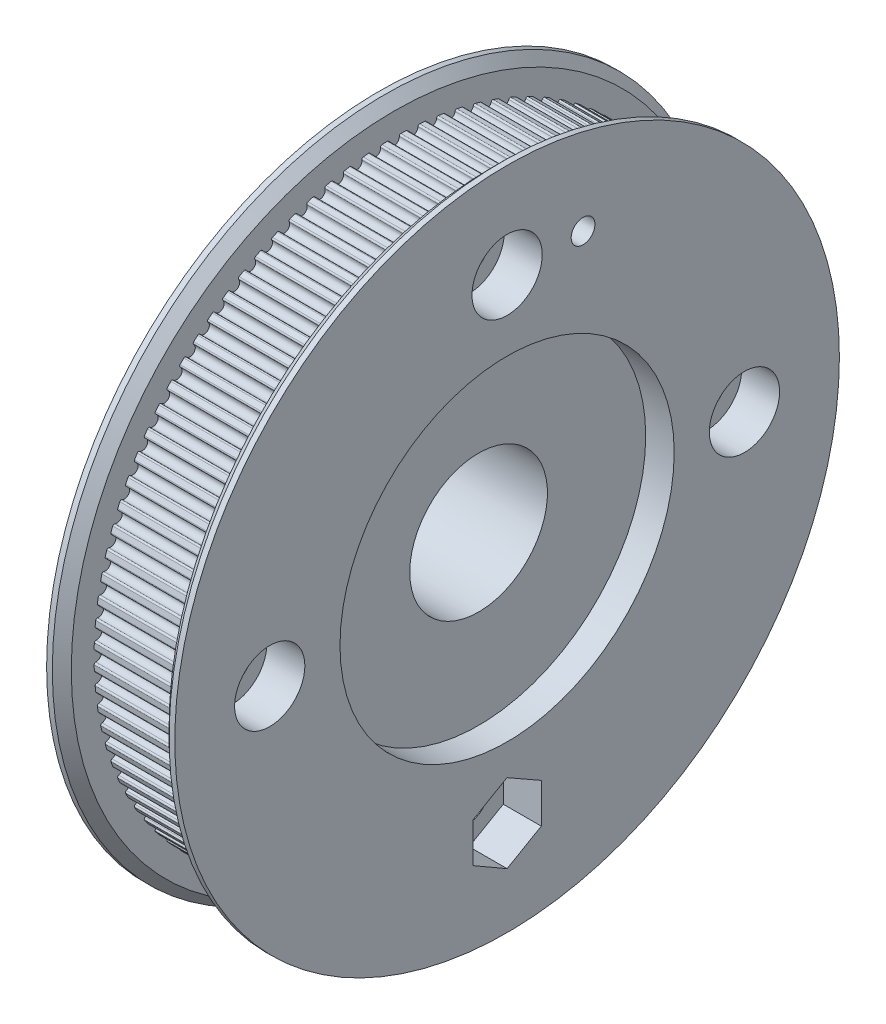
SolidWorks part; units mm, degrees
note: '?' marks a value the reader was unsure of.
ref_plane "Front Plane" through (0, 0, 0) normal (0, 0, 1) x (1, 0, 0)
ref_plane "Top Plane" through (0, 0, 0) normal (0, 1, 0) x (1, 0, 0)
ref_plane "Right Plane" through (0, 0, 0) normal (1, 0, 0) x (0, 0, -1)
sketch "Sketch1" plane through (0, 0, 0) normal (1, 0, 0) x (0, 0, -1)
  circle A0 centre (0, 0) radius 31.6
  circle A1 centre (0, 0) radius 7.25
  dimension "D1" = 63.2
  dimension "D2" = 14.5
extrude "Boss-Extrude1" add sketch "Sketch1" along normal blind 10.3
sketch "Sketch2" plane through (0, 0, 0) normal (1, 0, 0) x (0, 0, -1)
  circle A0 centre (0, 0) radius 31.39 construction
  circle A1 centre (0, 31.39) radius 0.55
  circle A2 centre (0, 0) radius 31.39 construction
  circle A3 centre (1.971, 31.3281) radius 0.55
  circle A4 centre (0, 0) radius 31.39 construction
  circle A5 centre (3.9342, 31.1425) radius 0.55
  circle A6 centre (0, 0) radius 31.39 construction
  circle A7 centre (5.8819, 30.834) radius 0.55
  circle A8 centre (0, 0) radius 31.39 construction
  circle A9 centre (7.8064, 30.4038) radius 0.55
  circle A10 centre (0, 0) radius 31.39 construction
  circle A11 centre (9.7, 29.8537) radius 0.55
  circle A12 centre (0, 0) radius 31.39 construction
  circle A13 centre (11.5554, 29.1857) radius 0.55
  circle A14 centre (0, 0) radius 31.39 construction
  circle A15 centre (13.3652, 28.4025) radius 0.55
  circle A16 centre (0, 0) radius 31.39 construction
  circle A17 centre (15.1222, 27.5073) radius 0.55
  circle A18 centre (0, 0) radius 31.39 construction
  circle A19 centre (16.8196, 26.5035) radius 0.55
  circle A20 centre (0, 0) radius 31.39 construction
  circle A21 centre (18.4506, 25.395) radius 0.55
  circle A22 centre (0, 0) radius 31.39 construction
  circle A23 centre (20.0087, 24.1864) radius 0.55
  circle A24 centre (0, 0) radius 31.39 construction
  circle A25 centre (21.4879, 22.8823) radius 0.55
  circle A26 centre (0, 0) radius 31.39 construction
  circle A27 centre (22.8823, 21.4879) radius 0.55
  circle A28 centre (0, 0) radius 31.39 construction
  circle A29 centre (24.1864, 20.0087) radius 0.55
  circle A30 centre (0, 0) radius 31.39 construction
  circle A31 centre (25.395, 18.4506) radius 0.55
  circle A32 centre (0, 0) radius 31.39 construction
  circle A33 centre (26.5035, 16.8196) radius 0.55
  circle A34 centre (0, 0) radius 31.39 construction
  circle A35 centre (27.5073, 15.1222) radius 0.55
  circle A36 centre (0, 0) radius 31.39 construction
  circle A37 centre (28.4025, 13.3652) radius 0.55
  circle A38 centre (0, 0) radius 31.39 construction
  circle A39 centre (29.1857, 11.5554) radius 0.55
  circle A40 centre (0, 0) radius 31.39 construction
  circle A41 centre (29.8537, 9.7) radius 0.55
  circle A42 centre (0, 0) radius 31.39 construction
  circle A43 centre (30.4038, 7.8064) radius 0.55
  circle A44 centre (0, 0) radius 31.39 construction
  circle A45 centre (30.834, 5.8819) radius 0.55
  circle A46 centre (0, 0) radius 31.39 construction
  circle A47 centre (31.1425, 3.9342) radius 0.55
  circle A48 centre (0, 0) radius 31.39 construction
  circle A49 centre (31.3281, 1.971) radius 0.55
  circle A50 centre (0, 0) radius 31.39 construction
  circle A51 centre (31.39, 0) radius 0.55
  circle A52 centre (0, 0) radius 31.39 construction
  circle A53 centre (31.3281, -1.971) radius 0.55
  circle A54 centre (0, 0) radius 31.39 construction
  circle A55 centre (31.1425, -3.9342) radius 0.55
  circle A56 centre (0, 0) radius 31.39 construction
  circle A57 centre (30.834, -5.8819) radius 0.55
  circle A58 centre (0, 0) radius 31.39 construction
  circle A59 centre (30.4038, -7.8064) radius 0.55
  circle A60 centre (0, 0) radius 31.39 construction
  circle A61 centre (29.8537, -9.7) radius 0.55
  circle A62 centre (0, 0) radius 31.39 construction
  circle A63 centre (29.1857, -11.5554) radius 0.55
  circle A64 centre (0, 0) radius 31.39 construction
  circle A65 centre (28.4025, -13.3652) radius 0.55
  circle A66 centre (0, 0) radius 31.39 construction
  circle A67 centre (27.5073, -15.1222) radius 0.55
  circle A68 centre (0, 0) radius 31.39 construction
  circle A69 centre (26.5035, -16.8196) radius 0.55
  circle A70 centre (0, 0) radius 31.39 construction
  circle A71 centre (25.395, -18.4506) radius 0.55
  circle A72 centre (0, 0) radius 31.39 construction
  circle A73 centre (24.1864, -20.0087) radius 0.55
  circle A74 centre (0, 0) radius 31.39 construction
  circle A75 centre (22.8823, -21.4879) radius 0.55
  circle A76 centre (0, 0) radius 31.39 construction
  circle A77 centre (21.4879, -22.8823) radius 0.55
  circle A78 centre (0, 0) radius 31.39 construction
  circle A79 centre (20.0087, -24.1864) radius 0.55
  circle A80 centre (0, 0) radius 31.39 construction
  circle A81 centre (18.4506, -25.395) radius 0.55
  circle A82 centre (0, 0) radius 31.39 construction
  circle A83 centre (16.8196, -26.5035) radius 0.55
  circle A84 centre (0, 0) radius 31.39 construction
  circle A85 centre (15.1222, -27.5073) radius 0.55
  circle A86 centre (0, 0) radius 31.39 construction
  circle A87 centre (13.3652, -28.4025) radius 0.55
  circle A88 centre (0, 0) radius 31.39 construction
  circle A89 centre (11.5554, -29.1857) radius 0.55
  circle A90 centre (0, 0) radius 31.39 construction
  circle A91 centre (9.7, -29.8537) radius 0.55
  circle A92 centre (0, 0) radius 31.39 construction
  circle A93 centre (7.8064, -30.4038) radius 0.55
  circle A94 centre (0, 0) radius 31.39 construction
  circle A95 centre (5.8819, -30.834) radius 0.55
  circle A96 centre (0, 0) radius 31.39 construction
  circle A97 centre (3.9342, -31.1425) radius 0.55
  circle A98 centre (0, 0) radius 31.39 construction
  circle A99 centre (1.971, -31.3281) radius 0.55
  circle A100 centre (0, 0) radius 31.39 construction
  circle A101 centre (0, -31.39) radius 0.55
  circle A102 centre (0, 0) radius 31.39 construction
  circle A103 centre (-1.971, -31.3281) radius 0.55
  circle A104 centre (0, 0) radius 31.39 construction
  circle A105 centre (-3.9342, -31.1425) radius 0.55
  circle A106 centre (0, 0) radius 31.39 construction
  circle A107 centre (-5.8819, -30.834) radius 0.55
  circle A108 centre (0, 0) radius 31.39 construction
  circle A109 centre (-7.8064, -30.4038) radius 0.55
  circle A110 centre (0, 0) radius 31.39 construction
  circle A111 centre (-9.7, -29.8537) radius 0.55
  circle A112 centre (0, 0) radius 31.39 construction
  circle A113 centre (-11.5554, -29.1857) radius 0.55
  circle A114 centre (0, 0) radius 31.39 construction
  circle A115 centre (-13.3652, -28.4025) radius 0.55
  circle A116 centre (0, 0) radius 31.39 construction
  circle A117 centre (-15.1222, -27.5073) radius 0.55
  circle A118 centre (0, 0) radius 31.39 construction
  circle A119 centre (-16.8196, -26.5035) radius 0.55
  circle A120 centre (0, 0) radius 31.39 construction
  circle A121 centre (-18.4506, -25.395) radius 0.55
  circle A122 centre (0, 0) radius 31.39 construction
  circle A123 centre (-20.0087, -24.1864) radius 0.55
  circle A124 centre (0, 0) radius 31.39 construction
  circle A125 centre (-21.4879, -22.8823) radius 0.55
  circle A126 centre (0, 0) radius 31.39 construction
  circle A127 centre (-22.8823, -21.4879) radius 0.55
  circle A128 centre (0, 0) radius 31.39 construction
  circle A129 centre (-24.1864, -20.0087) radius 0.55
  circle A130 centre (0, 0) radius 31.39 construction
  circle A131 centre (-25.395, -18.4506) radius 0.55
  circle A132 centre (0, 0) radius 31.39 construction
  circle A133 centre (-26.5035, -16.8196) radius 0.55
  circle A134 centre (0, 0) radius 31.39 construction
  circle A135 centre (-27.5073, -15.1222) radius 0.55
  circle A136 centre (0, 0) radius 31.39 construction
  circle A137 centre (-28.4025, -13.3652) radius 0.55
  circle A138 centre (0, 0) radius 31.39 construction
  circle A139 centre (-29.1857, -11.5554) radius 0.55
  circle A140 centre (0, 0) radius 31.39 construction
  circle A141 centre (-29.8537, -9.7) radius 0.55
  circle A142 centre (0, 0) radius 31.39 construction
  circle A143 centre (-30.4038, -7.8064) radius 0.55
  circle A144 centre (0, 0) radius 31.39 construction
  circle A145 centre (-30.834, -5.8819) radius 0.55
  circle A146 centre (0, 0) radius 31.39 construction
  circle A147 centre (-31.1425, -3.9342) radius 0.55
  circle A148 centre (0, 0) radius 31.39 construction
  circle A149 centre (-31.3281, -1.971) radius 0.55
  circle A150 centre (0, 0) radius 31.39 construction
  circle A151 centre (-31.39, 0) radius 0.55
  circle A152 centre (0, 0) radius 31.39 construction
  circle A153 centre (-31.3281, 1.971) radius 0.55
  circle A154 centre (0, 0) radius 31.39 construction
  circle A155 centre (-31.1425, 3.9342) radius 0.55
  circle A156 centre (0, 0) radius 31.39 construction
  circle A157 centre (-30.834, 5.8819) radius 0.55
  circle A158 centre (0, 0) radius 31.39 construction
  circle A159 centre (-30.4038, 7.8064) radius 0.55
  circle A160 centre (0, 0) radius 31.39 construction
  circle A161 centre (-29.8537, 9.7) radius 0.55
  circle A162 centre (0, 0) radius 31.39 construction
  circle A163 centre (-29.1857, 11.5554) radius 0.55
  circle A164 centre (0, 0) radius 31.39 construction
  circle A165 centre (-28.4025, 13.3652) radius 0.55
  circle A166 centre (0, 0) radius 31.39 construction
  circle A167 centre (-27.5073, 15.1222) radius 0.55
  circle A168 centre (0, 0) radius 31.39 construction
  circle A169 centre (-26.5035, 16.8196) radius 0.55
  circle A170 centre (0, 0) radius 31.39 construction
  circle A171 centre (-25.395, 18.4506) radius 0.55
  circle A172 centre (0, 0) radius 31.39 construction
  circle A173 centre (-24.1864, 20.0087) radius 0.55
  circle A174 centre (0, 0) radius 31.39 construction
  circle A175 centre (-22.8823, 21.4879) radius 0.55
  circle A176 centre (0, 0) radius 31.39 construction
  circle A177 centre (-21.4879, 22.8823) radius 0.55
  circle A178 centre (0, 0) radius 31.39 construction
  circle A179 centre (-20.0087, 24.1864) radius 0.55
  circle A180 centre (0, 0) radius 31.39 construction
  circle A181 centre (-18.4506, 25.395) radius 0.55
  circle A182 centre (0, 0) radius 31.39 construction
  circle A183 centre (-16.8196, 26.5035) radius 0.55
  circle A184 centre (0, 0) radius 31.39 construction
  circle A185 centre (-15.1222, 27.5073) radius 0.55
  circle A186 centre (0, 0) radius 31.39 construction
  circle A187 centre (-13.3652, 28.4025) radius 0.55
  circle A188 centre (0, 0) radius 31.39 construction
  circle A189 centre (-11.5554, 29.1857) radius 0.55
  circle A190 centre (0, 0) radius 31.39 construction
  circle A191 centre (-9.7, 29.8537) radius 0.55
  circle A192 centre (0, 0) radius 31.39 construction
  circle A193 centre (-7.8064, 30.4038) radius 0.55
  circle A194 centre (0, 0) radius 31.39 construction
  circle A195 centre (-5.8819, 30.834) radius 0.55
  circle A196 centre (0, 0) radius 31.39 construction
  circle A197 centre (-3.9342, 31.1425) radius 0.55
  circle A198 centre (0, 0) radius 31.39 construction
  circle A199 centre (-1.971, 31.3281) radius 0.55
  point P305 (0, 0)
  dimension "D1" = 62.78
  dimension "D2" = 1.1
  dimension "D3" = 100
extrude "Cut-Extrude1" cut sketch "Sketch2" along normal up to surface (10.3 mm away) up to face at (10.3, 0, -31.6)
fillet "Fillet1" radius 0.16 200 edges at (5.15, 31.5959, -0.51) (5.15, 31.5959, 0.51) (5.15, 31.5656, 1.4749) (5.15, 31.5015, 2.4929) (5.15, 21.2571, -23.3815) (5.15, 22.0007, -22.6833) (5.15, 22.6833, -22.0007) (5.15, 23.3815, -21.2571) (5.15, 19.747, -24.6701) (5.15, 20.5329, -24.02) (5.15, 18.159, -25.8614) (5.15, 18.9842, -25.2618) (5.15, 16.4993, -26.9506) (5.15, 17.3605, -26.404) (5.15, 14.7745, -27.9334) (5.15, 15.6684, -27.442) (5.15, 12.9914, -28.806) (5.15, 13.9143, -28.3717) (5.15, 11.157, -29.5649) (5.15, 12.1054, -29.1894) (5.15, 24.02, -20.5329) (5.15, 24.6701, -19.747) (5.15, 25.2618, -18.9842) (5.15, 25.8614, -18.159) (5.15, 26.404, -17.3605) (5.15, 26.9506, -16.4993) (5.15, 27.442, -15.6684) (5.15, 27.9334, -14.7745) (5.15, 28.3717, -13.9143) (5.15, 28.806, -12.9914) (5.15, 29.1894, -12.1054) (5.15, 29.5649, -11.157) (5.15, 29.8919, -10.2487) (5.15, 30.2071, -9.2786) (5.15, 30.4764, -8.3516) (5.15, 30.7301, -7.3636) (5.15, 30.9407, -6.4215) (5.15, 31.1318, -5.4195) (5.15, 31.2828, -4.466) (5.15, 31.4107, -3.454) (5.15, 31.5015, -2.4929) (5.15, 31.5656, -1.4749) (5.15, 31.4107, 3.454) (5.15, 31.2828, 4.466) (5.15, 31.1318, 5.4195) (5.15, 30.9407, 6.4215) (5.15, 30.7301, 7.3636) (5.15, 30.4764, 8.3516) (5.15, 30.2071, 9.2786) (5.15, 29.8919, 10.2487) (5.15, 29.5649, 11.157) (5.15, 29.1894, 12.1054) (5.15, 28.806, 12.9914) (5.15, 28.3717, 13.9143) (5.15, 27.9334, 14.7745) (5.15, 27.442, 15.6684) (5.15, 26.9506, 16.4993) (5.15, 26.404, 17.3605) (5.15, 25.8614, 18.159) (5.15, 25.2618, 18.9842) (5.15, 24.6701, 19.747) (5.15, 24.02, 20.5329) (5.15, 23.3815, 21.2571) (5.15, 22.6833, 22.0007) (5.15, 22.0007, 22.6833) (5.15, 21.2571, 23.3815) (5.15, 20.5329, 24.02) (5.15, 19.747, 24.6701) (5.15, 18.9842, 25.2618) (5.15, 18.159, 25.8614) (5.15, 17.3605, 26.404) (5.15, 16.4993, 26.9506) (5.15, 15.6684, 27.442) (5.15, 14.7745, 27.9334) (5.15, 13.9143, 28.3717) (5.15, 12.9914, 28.806) (5.15, 12.1054, 29.1894) (5.15, 11.157, 29.5649) (5.15, 10.2487, 29.8919) (5.15, 9.2786, 30.2071) (5.15, 8.3516, 30.4764) (5.15, 7.3636, 30.7301) (5.15, 6.4215, 30.9407) (5.15, 5.4195, 31.1318) (5.15, 4.466, 31.2828) (5.15, 3.454, 31.4107) (5.15, 2.4929, 31.5015) (5.15, 1.4749, 31.5656) (5.15, 0.51, 31.5959) (5.15, -0.51, 31.5959) (5.15, -1.4749, 31.5656) (5.15, -2.4929, 31.5015) (5.15, -3.454, 31.4107) (5.15, -4.466, 31.2828) (5.15, -5.4195, 31.1318) (5.15, -6.4215, 30.9407) (5.15, -7.3636, 30.7301) (5.15, -8.3516, 30.4764) (5.15, -9.2786, 30.2071) (5.15, -10.2487, 29.8919) (5.15, -11.157, 29.5649) (5.15, -12.1054, 29.1894) (5.15, -12.9914, 28.806) (5.15, -13.9143, 28.3717) (5.15, -14.7745, 27.9334) (5.15, -15.6684, 27.442) (5.15, -16.4993, 26.9506) (5.15, -17.3605, 26.404) (5.15, -18.159, 25.8614) (5.15, -18.9842, 25.2618) (5.15, -19.747, 24.6701) (5.15, -20.5329, 24.02) (5.15, -21.2571, 23.3815) (5.15, -22.0007, 22.6833) (5.15, -22.6833, 22.0007) (5.15, -23.3815, 21.2571) (5.15, -24.02, 20.5329) (5.15, -24.6701, 19.747) (5.15, -25.2618, 18.9842) (5.15, -25.8614, 18.159) (5.15, -26.404, 17.3605) (5.15, -26.9506, 16.4993) (5.15, -27.442, 15.6684) (5.15, -27.9334, 14.7745) (5.15, -28.3717, 13.9143) (5.15, -28.806, 12.9914) (5.15, -29.1894, 12.1054) (5.15, -29.5649, 11.157) (5.15, -29.8919, 10.2487) (5.15, -30.2071, 9.2786) (5.15, -30.4764, 8.3516) (5.15, -30.7301, 7.3636) (5.15, -30.9407, 6.4215) (5.15, -31.1318, 5.4195) (5.15, -31.2828, 4.466) (5.15, -31.4107, 3.454) (5.15, -31.5015, 2.4929) (5.15, -31.5656, 1.4749) (5.15, -31.5959, 0.51) (5.15, -31.5959, -0.51) (5.15, -31.5656, -1.4749) (5.15, -31.5015, -2.4929) (5.15, -31.4107, -3.454) (5.15, -31.2828, -4.466) (5.15, -31.1318, -5.4195) (5.15, -30.9407, -6.4215) (5.15, -30.7301, -7.3636) (5.15, -30.4764, -8.3516) (5.15, -30.2071, -9.2786) (5.15, -29.8919, -10.2487) (5.15, -29.5649, -11.157) (5.15, -29.1894, -12.1054) (5.15, -28.806, -12.9914) (5.15, -28.3717, -13.9143) (5.15, -27.9334, -14.7745) (5.15, -27.442, -15.6684) (5.15, -26.9506, -16.4993) (5.15, -26.404, -17.3605) (5.15, -25.8614, -18.159) (5.15, -25.2618, -18.9842) (5.15, -24.6701, -19.747) (5.15, -24.02, -20.5329) (5.15, -23.3815, -21.2571) (5.15, -22.6833, -22.0007) (5.15, -22.0007, -22.6833) (5.15, -21.2571, -23.3815) (5.15, -20.5329, -24.02) (5.15, -19.747, -24.6701) (5.15, -18.9842, -25.2618) (5.15, -18.159, -25.8614) (5.15, -17.3605, -26.404) (5.15, -16.4993, -26.9506) (5.15, -15.6684, -27.442) (5.15, -14.7745, -27.9334) (5.15, -13.9143, -28.3717) (5.15, -12.9914, -28.806) (5.15, -12.1054, -29.1894) (5.15, -11.157, -29.5649) (5.15, -10.2487, -29.8919) (5.15, -9.2786, -30.2071) (5.15, -8.3516, -30.4764) (5.15, -7.3636, -30.7301) (5.15, -6.4215, -30.9407) (5.15, -5.4195, -31.1318) (5.15, -4.466, -31.2828) (5.15, -3.454, -31.4107) (5.15, -2.4929, -31.5015) (5.15, -1.4749, -31.5656) (5.15, 9.2786, -30.2071) (5.15, 10.2487, -29.8919) (5.15, 7.3636, -30.7301) (5.15, 8.3516, -30.4764) (5.15, 5.4195, -31.1318) (5.15, 6.4215, -30.9407) (5.15, 3.454, -31.4107) (5.15, 4.466, -31.2828) (5.15, 1.4749, -31.5656) (5.15, 2.4929, -31.5015) (5.15, -0.51, -31.5959) (5.15, 0.51, -31.5959)
ref_axis "Axis1" through (10.3, 0, 0) along (-1, 0, 0)?
sketch "Sketch3" plane through (10.3, 0, 0) normal (1, 0, 0) x (0, 0, -1)
  circle A0 centre (0, 0) radius 35
  circle A1 centre (0, 0) radius 7.25
  circle A2 centre (0, 0) radius 7.25 construction
  dimension "D1" = 70
extrude "Boss-Extrude2" add sketch "Sketch3" along normal blind 1.6
sketch "Sketch6" plane through (11.9, 0, 0) normal (1, 0, 0) x (0, 0, -1)
  line L0 (0, 25) -> (8, 25) construction
  circle A0 centre (0, -25) radius 2.2
  circle A3 centre (-25, 0) radius 2.2
  circle A4 centre (0, 25) radius 2.2
  circle A5 centre (25, 0) radius 2.2
  circle A6 centre (8, 25) radius 1.25
  point P13 (0, 0)
  dimension "D1" = 4.4
  dimension "D5" = 2.5
  dimension "D2" = 25
  dimension "D4" = 8
  dimension "D3" = 4
sketch "Sketch7" plane through (11.9, 0, 0) normal (1, 0, 0) x (0, 0, -1)
  line L0 (0, -29.1569) -> (3.6, -27.0785)
  line L1 (3.6, -27.0785) -> (3.6, -22.9071)
  line L2 (3.6, -22.9071) -> (-0.0125, -20.8503)
  line L3 (-0.0125, -20.8503) -> (-3.6, -22.9215)
  line L4 (-3.6, -22.9215) -> (-3.6, -27.0785)
  line L5 (-3.6, -27.0785) -> (0, -29.1569)
  circle A0 centre (25, 0) radius 3.7
  circle A1 centre (0, 25) radius 3.7
  circle A2 centre (-25, 0) radius 3.7
  circle A5 centre (0, -25) radius 3.6 construction
  circle A9 centre (0, 25) radius 2.2 construction
  circle A10 centre (0, -25) radius 2.2 construction
  circle A11 centre (25, 0) radius 2.2 construction
  point P12 (0, 0)
  dimension "D1" = 7.4
  dimension "D3" = 7.2
extrude "Cut-Extrude4" cut sketch "Sketch7" against normal blind 4 contours A0 | A2 | A1 | L3 L4 L5 L0 L1 L2
chamfer "Chamfer1" distance 1 angle 45 1 edges at (10.3, 0, -35)
sketch "Sketch8" plane through (11.9, 0, 0) normal (1, 0, 0) x (0, 0, -1)
  circle A0 centre (0, 0) radius 17.6
  dimension "D1" = 35.2
extrude "Cut-Extrude7" cut sketch "Sketch8" against normal blind 3
sketch "草图1" plane through (0, 0, 0) normal (-1, 0, 0) x (0, 0, 1)
  circle A0 centre (0, 0) radius 35
  dimension "D1" = 70
extrude "凸台-拉伸1" add sketch "草图1" along normal blind 1.6
chamfer "倒角1" distance 1 angle 45 1 edges at (0, 0, 35)
sketch "草图2" plane through (-1.6, 0, 0) normal (-1, 0, 0) x (0, 0, 1)
  line L0 (0, 25) -> (-8, 25) construction
  circle A0 centre (0, -25) radius 2
  circle A1 centre (-25, 0) radius 2
  circle A2 centre (25, 0) radius 2
  circle A3 centre (0, 25) radius 2
  circle A4 centre (0, 0) radius 7.25
  circle A5 centre (-8, 25) radius 1.25
  circle A6 centre (0, -25) radius 2.2 construction
  dimension "D1" = 4
  dimension "D2" = 14.5
  dimension "D3" = 8
extrude "切除-拉伸1" cut sketch "草图2" against normal through all
